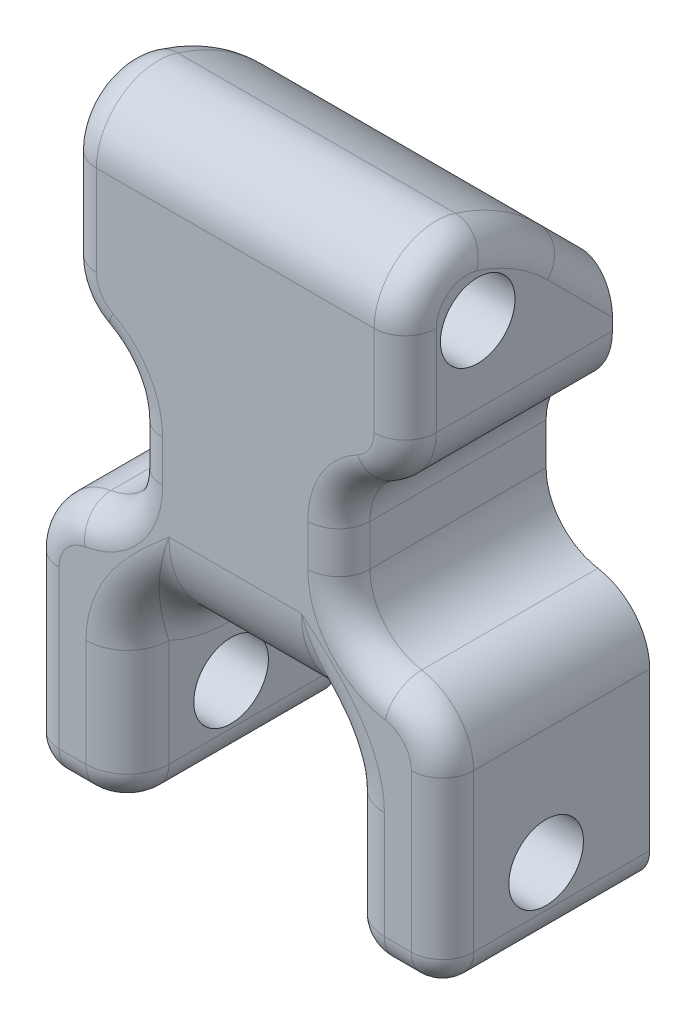
SolidWorks part; units mm, degrees
ref_plane "Alzado" through (0, 0, 0) normal (0, 0, 1) x (1, 0, 0)
ref_plane "Planta" through (0, 0, 0) normal (0, 1, 0) x (1, 0, 0)
ref_plane "Vista lateral" through (0, 0, 0) normal (1, 0, 0) x (0, 0, -1)
sketch "Croquis1" plane through (0, 0, 0) normal (0, 0, 1) x (1, 0, 0)
  line L0 (0, -1.4774) -> (0, 10.928) construction
  line L1 (10, 0) -> (5.2, 0)
  line L2 (5, 12) -> (5, 20)
  line L3 (8.2, 30) -> (-8.2, 30)
  line L4 (-5, 12) -> (-5, 20)
  line L5 (-5, 20) -> (-8.2, 20)
  line L6 (-5.2, 0) -> (-10, 0)
  line L7 (-8.2, 20) -> (-8.2, 30)
  line L8 (5, 20) -> (8.2, 20)
  line L9 (8.2, 20) -> (8.2, 30)
  line L10 (-5, 12) -> (-10, 12)
  line L11 (-10, 12) -> (-10, 0)
  line L12 (5, 12) -> (10, 12)
  line L13 (10, 12) -> (10, 0)
  line L15 (-5.2, 0) -> (-5.2, 8)
  line L16 (-5.2, 8) -> (5.2, 8)
  line L17 (5.2, 0) -> (5.2, 8)
  dimension "D1" = 30
  dimension "D2" = 12
  dimension "D3" = 16.4
  dimension "D4" = 10
  dimension "D5" = 20
  dimension "D6" = 8
  dimension "D7" = 10.4
  dimension "D8" = 10
extrude "Saliente-Extruir1" add sketch "Croquis1" along normal blind 10
chamfer "Chaflán1" distance 5 angle 45 1 edges at (0, 30, 0)
fillet "Redondeo1" radius 10 1 edges at (0, 30, 5)
sketch "Croquis4" plane through (0, 0, 0) normal (-1, 0, 0) x (0, 0, 1)
  line L0 (10, 30) -> (9.1421, 30) construction
  line L1 (10, 0) -> (0, 0) construction
  line L2 (10, 30) -> (10, 20) construction
  line L3 (10, 12) -> (10, 0) construction
  circle A0 centre (6.5, 26) radius 1.8
  circle A1 centre (5, 3.5) radius 1.8
  dimension "D1" = 3.6
  dimension "D2" = 4
  dimension "D3" = 5
  dimension "D4" = 3.5
  dimension "D5" = 3.5
extrude "Cortar-Extruir3" cut sketch "Croquis4" against normal through all both and the other way through all
fillet "Redondeo5" radius 3 4 edges at (-5, 20, 5) (5, 20, 5) (5, 12, 5) (-5, 12, 5)
fillet "Redondeo6" radius 3 4 edges at (-8.2, 20, 5) (8.2, 20, 5) (10, 12, 5) (-10, 12, 5)
fillet "Redondeo7" radius 3 1 edges at (0, 30, 10)
fillet "Redondeo13" radius 5 1 edges at (0, 8, 10)
fillet "Redondeo14" radius 2 4 edges at (5.2, 9.4645, 8.5355) (-5.2, 9.4645, 8.5355) (5.2, 8, 2.5) (-5.2, 8, 2.5)
fillet "Redondeo15" radius 2 4 edges at (4.934, 9.6773, 10) (-4.934, 9.6773, 10) (5.2, 4.0505, 10) (-5.2, 4.0505, 10)
fillet "Redondeo10" radius 1.5 2 edges at (10, 0, 5) (-10, 0, 5)
fillet "Redondeo8" radius 1.5 28 edges at (8.2, 26.0355, 1.0355) (8.2, 28.5346, 3.9306) (8.2, 24.4854, 10) (7.769, 20.7574, 10) (5.431, 18.5492, 10) (-8.2, 26.0355, 1.0355) (-8.2, 28.5346, 3.9306) (-8.2, 24.4854, 10) (-7.769, 20.7574, 10) (-5.431, 18.5492, 10) (5, 16, 10) (-5, 16, 10) (10, 5.292, 10) (9.2913, 11.0204, 10) (5.7087, 13.0635, 10) (-10, 5.292, 10) (-9.2913, 11.0204, 10) (-5.7087, 13.0635, 10) (7.85, 0, 10) (9.5607, 0.4393, 10) (-7.85, 0, 10) (-9.5607, 0.4393, 10) (8.2, 29.0884, 8.7672) (-8.2, 29.0884, 8.7672) (5.2, 0, 4) (-5.2, 0, 4) (5.7858, 0, 9.4142) (-5.7858, 0, 9.4142)
